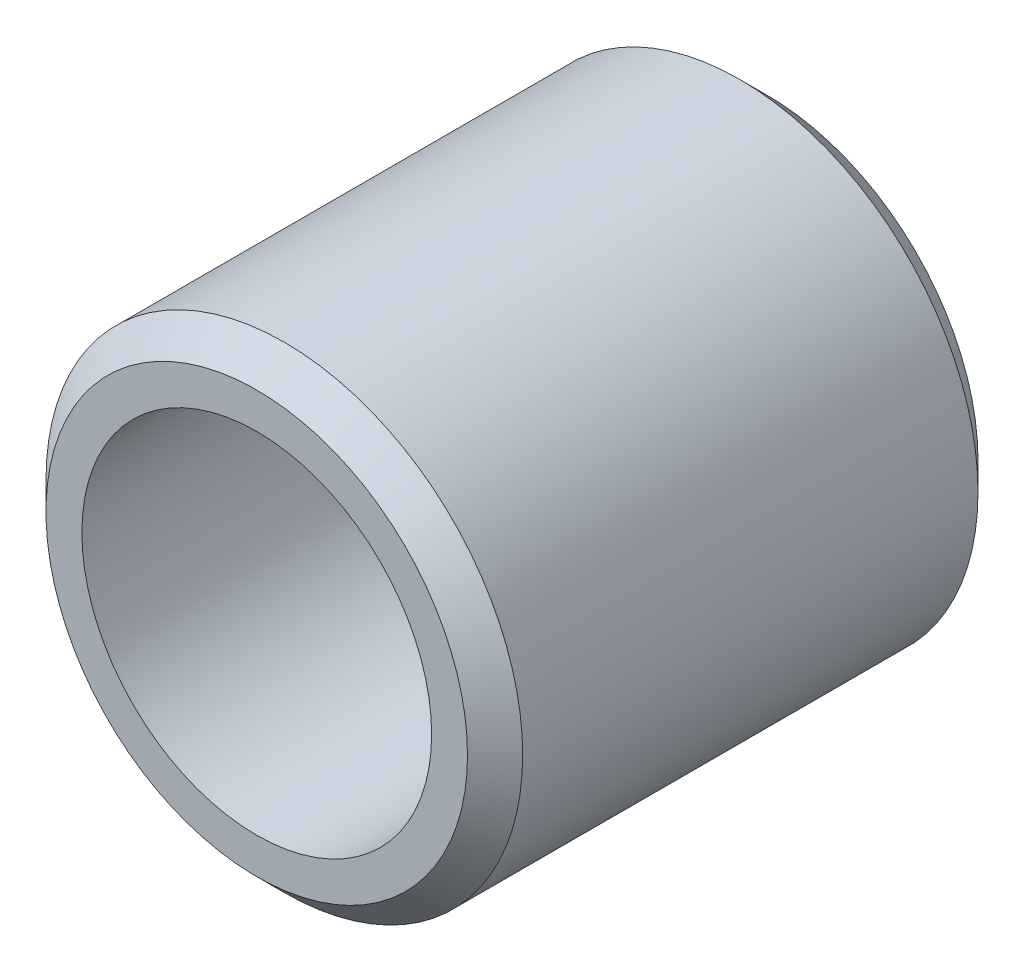
SolidWorks part; units mm, degrees
material "Brass"
ref_plane "Front Plane" through (0, 0, 0) normal (0, 0, 1) x (1, 0, 0)
ref_plane "Top Plane" through (0, 0, 0) normal (0, 1, 0) x (1, 0, 0)
ref_plane "Right Plane" through (0, 0, 0) normal (1, 0, 0) x (0, 0, -1)
sketch "Sketch1" plane through (0, 0, 0) normal (1, 0, 0) x (0, 0, -1)
  line L0 (-4.699, 3.8798) -> (-4.699, 3.2195)
  line L1 (-4.699, 3.2195) -> (4.699, 3.2195)
  line L2 (4.699, 3.2195) -> (4.699, 3.8798)
  line L3 (4.699, 3.8798) -> (4.191, 4.3879)
  line L4 (4.191, 4.3879) -> (-4.191, 4.3879)
  line L5 (-4.191, 4.3879) -> (-4.699, 3.8798)
  line L6 (4.699, 0) -> (-4.699, 0) construction
revolve "Revolve1" add sketch "Sketch1" angle 360 about L6 reverse direction yes
ref_plane "bushing XY" through (0, 0, 0) normal (0, 0, 1) x (1, 0, 0)
ref_plane "bushing XZ" through (0, 0, 0) normal (0, -1, 0) x (-1, 0, 0)
ref_plane "bushing YZ" through (0, 0, 0) normal (1, 0, 0) x (0, 0, -1)
ref_axis "bushing X" through (-80.9, 0, 0) along (1, 0, 0)
ref_axis "bushing Y" through (0, -50, 0) along (0, 1, 0)
ref_axis "bushing Z" through (0, 0, 80.9) along (0, 0, -1)
sketch3d "bushing"
  point P0 (0, 0, 0)
ref_plane "id1 XY" through (0, 0, 0) normal (0, 0, 1) x (1, 0, 0)
ref_plane "id1 XZ" through (0, 0, 0) normal (0, -1, 0) x (-1, 0, 0)
ref_plane "id1 YZ" through (-3.2195, 0, 0) normal (1, 0, 0) x (0, 0, -1)
ref_axis "id1 X" through (-80.9, 0, 0) along (1, 0, 0)
ref_axis "id1 Y" through (-3.2195, -50, 0) along (0, 1, 0)
ref_axis "id1 Z" through (-3.2195, 0, 80.9) along (0, 0, -1)
sketch3d "id1"
  point P0 (-3.2195, 0, 0)
ref_plane "id2 XY" through (0, 0, 0) normal (0, 0, 1) x (1, 0, 0)
ref_plane "id2 XZ" through (0, 0, 0) normal (0, -1, 0) x (-1, 0, 0)
ref_plane "id2 YZ" through (3.2195, 0, 0) normal (1, 0, 0) x (0, 0, -1)
ref_axis "id2 X" through (-80.9, 0, 0) along (1, 0, 0)
ref_axis "id2 Y" through (3.2195, -50, 0) along (0, 1, 0)
ref_axis "id2 Z" through (3.2195, 0, 80.9) along (0, 0, -1)
sketch3d "id2"
  point P0 (3.2195, 0, 0)
ref_plane "id3 XY" through (0, 0, -4.699) normal (0, 0, -1) x (-1, 0, 0)
ref_plane "id3 XZ" through (0, 0, 0) normal (-1, 0, 0) x (0, 0, 1)
ref_plane "id3 YZ" through (0, 0, 0) normal (0, 1, 0) x (1, 0, 0)
ref_axis "id3 X" through (0, -50, -4.699) along (0, 1, 0)
ref_axis "id3 Y" through (-80.9, 0, -4.699) along (1, 0, 0)
ref_axis "id3 Z" through (0, 0, -50) along (0, 0, 1)
sketch3d "id3"
  point P0 (0, 0, -4.699)
ref_plane "id4 XY" through (0, 0, 4.699) normal (0, 0, 1) x (1, 0, 0)
ref_plane "id4 XZ" through (0, 0, 0) normal (1, 0, 0) x (0, 0, -1)
ref_plane "id4 YZ" through (0, 0, 0) normal (0, 1, 0) x (1, 0, 0)
ref_axis "id4 X" through (0, -50, 4.699) along (0, 1, 0)
ref_axis "id4 Y" through (80.9, 0, 4.699) along (-1, 0, 0)
ref_axis "id4 Z" through (0, 0, 50) along (0, 0, -1)
sketch3d "id4"
  point P0 (0, 0, 4.699)
